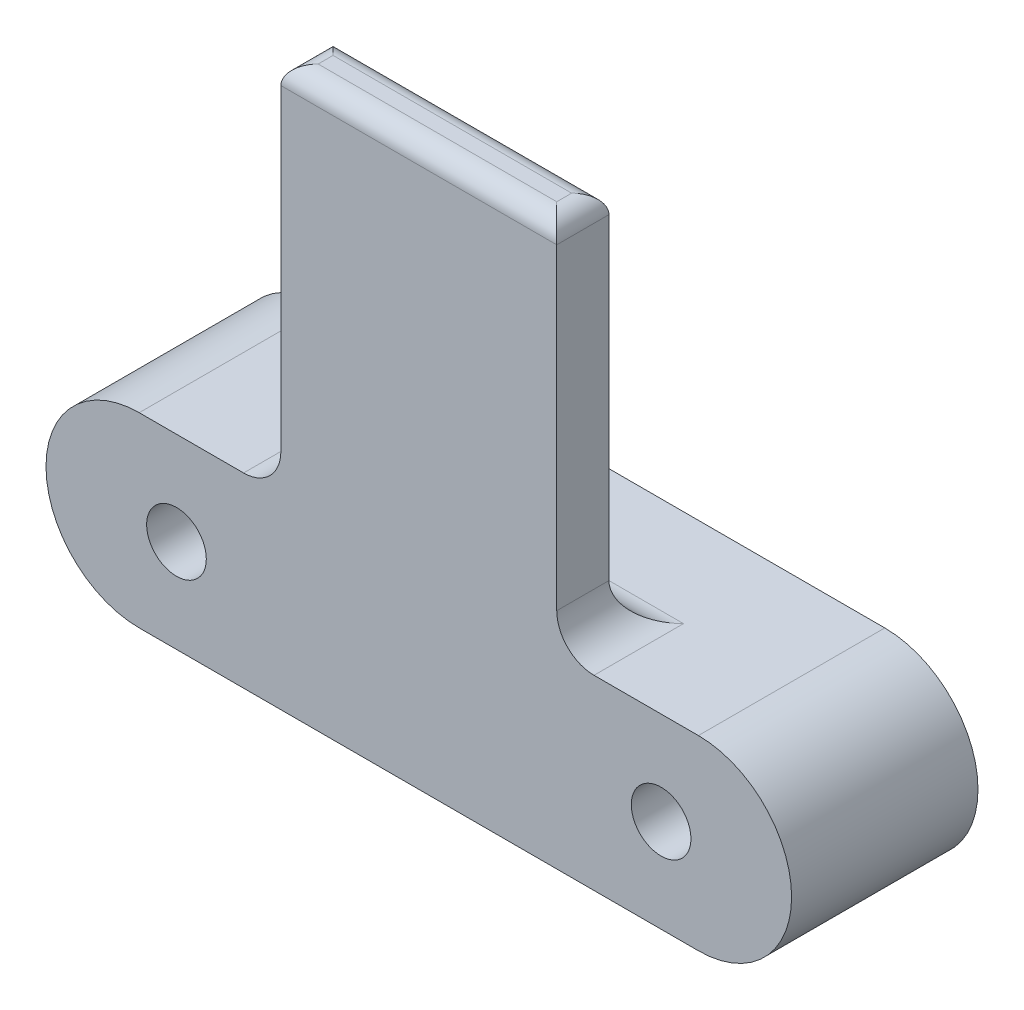
SolidWorks part; units mm, degrees
ref_plane "Спереди" through (0, 0, 0) normal (0, 0, 1) x (1, 0, 0)
ref_plane "Сверху" through (0, 0, 0) normal (0, 1, 0) x (1, 0, 0)
ref_plane "Справа" through (0, 0, 0) normal (1, 0, 0) x (0, 0, -1)
sketch "Эскиз1" plane through (0, 0, 0) normal (0, 0, 1) x (1, 0, 0)
  line L0 (-20, 0) -> (20, 0) construction
  line L1 (-20, -5) -> (20, -5)
  line L2 (-20, -5) -> (-20, 5)
  line L3 (-20, 5) -> (20, 5)
  line L4 (20, -5) -> (20, 5)
  line L5 (-20, -5) -> (20, 5) construction
  line L6 (-20, 5) -> (20, -5) construction
  line L7 (0, 5) -> (0, -5) construction
  circle A0 centre (-13, 0) radius 1.6
  circle A1 centre (13, 0) radius 1.6
  point P0 (0, 0)
  dimension "D1" = 3.2
  dimension "D2" = 13
  dimension "D3" = 40
  dimension "D4" = 10
extrude "Бобышка-Вытянуть1" add sketch "Эскиз1" along normal mid plane 10
fillet "Скругление1" 2 edges at (-20, 5, 0) (-20, -5, 0) type full round first side face at (0, 5, 0) second side face at (0, -5, 0) middle face at (-20, 0, 0)
fillet "Скругление2" 2 edges at (20, 5, 0) (20, -5, 0) type full round first side face at (2.5, 5, 0) second side face at (2.5, -5, 0) middle face at (20, 0, 0)
sketch "Эскиз2" plane through (0, 0, 5) normal (0, 0, 1) x (1, 0, 0)
  line L0 (0, 0) -> (0, 21.925) construction
  line L1 (-7.4, 5) -> (-7.4, 25)
  line L2 (15, 5) -> (-15, 5) construction
  line L3 (7.4, 5) -> (7.4, 25)
  line L4 (-7.4, 25) -> (7.4, 25)
  line L5 (7.4, 5) -> (-7.4, 5)
  dimension "D1" = 7.4
  dimension "D2" = 20
extrude "Бобышка-Вытянуть2" add sketch "Эскиз2" against normal blind 2.8
fillet "Скругление3" radius 2 3 edges at (0, 5, 2.2) (-7.4, 5, 3.6) (7.4, 5, 3.6)
fillet "Скругление4" radius 1 4 edges at (-7.4, 25, 3.6) (0, 25, 2.2) (7.4, 25, 3.6) (0, 25, 5)
